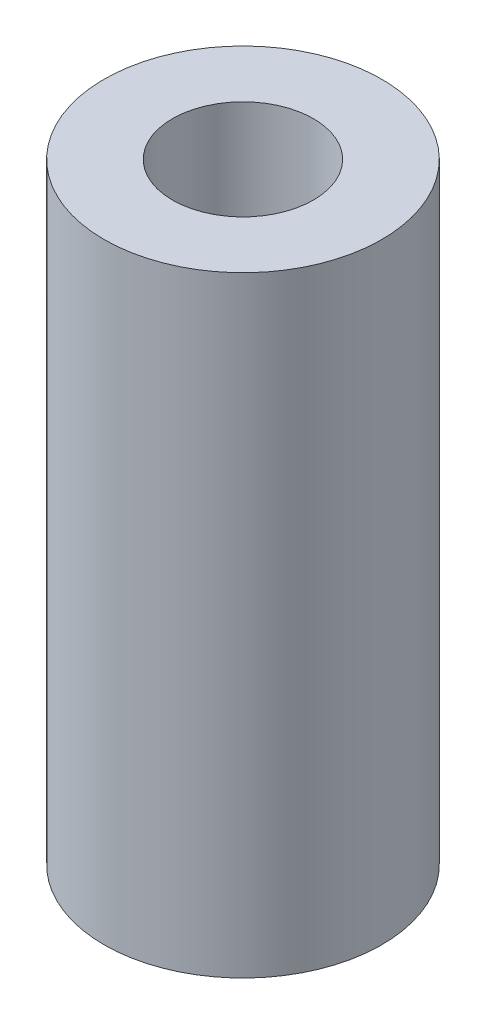
SolidWorks part; units mm, degrees
ref_plane "Front Plane" through (0, 0, 0) normal (0, 0, 1) x (1, 0, 0)
ref_plane "Top Plane" through (0, 0, 0) normal (0, 1, 0) x (1, 0, 0)
ref_plane "Right Plane" through (0, 0, 0) normal (1, 0, 0) x (0, 0, -1)
sketch "Sketch1" plane through (0, 0, 0) normal (0, 1, 0) x (1, 0, 0)
  circle A0 centre (0, 0) radius 6.35
  arc A4 (2.2922, 5.9218) -> (-4.4275, -4.5518) centre (0, 0) ccw construction
  circle A5 centre (0, 0) radius 3.2258
  circle A6 centre (0, 0) radius 3.2258
  dimension "D1" = 0.0508
extrude "Boss-Extrude1" add sketch "Sketch1" along normal up to surface (27.9373 mm away)
